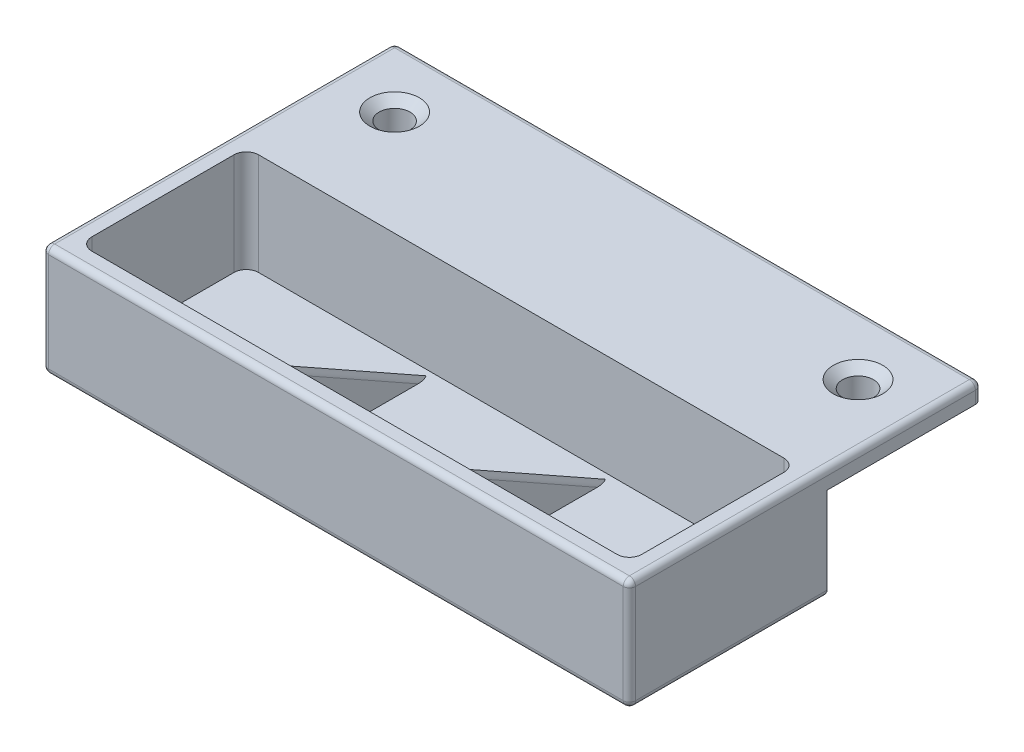
SolidWorks part; units mm, degrees
ref_plane "Front Plane" through (0, 0, 0) normal (0, 0, 1) x (1, 0, 0)
ref_plane "Top Plane" through (0, 0, 0) normal (0, 1, 0) x (1, 0, 0)
ref_plane "Right Plane" through (0, 0, 0) normal (1, 0, 0) x (0, 0, -1)
sketch "Sketch2" plane through (0, 0, 0) normal (0, 1, 0) x (1, 0, 0)
  line L1 (-47.5, 28.5) -> (47.5, 28.5)
  line L2 (-47.5, 28.5) -> (-47.5, -28.5)
  line L3 (-47.5, -28.5) -> (47.5, -28.5)
  line L4 (47.5, 28.5) -> (47.5, -28.5)
  line L5 (-47.5, 28.5) -> (47.5, -28.5) construction
  line L6 (-47.5, -28.5) -> (47.5, 28.5) construction
  point P0 (0, 0)
  dimension "D1" = 95
  dimension "D2" = 57
extrude "Boss-Extrude1" add sketch "Sketch2" along normal blind 18
sketch "Sketch3" plane through (47.5, 0, 0) normal (1, 0, 0) x (0, 0, -1)
  line L1 (28.5, 0) -> (3.5, 0)
  line L2 (28.5, 0) -> (28.5, 15)
  line L3 (28.5, 15) -> (3.5, 15)
  line L4 (3.5, 0) -> (3.5, 15)
  dimension "D1" = 15
  dimension "D2" = 25
extrude "Cut-Extrude1" cut sketch "Sketch3" against normal through all
sketch "Sketch4" plane through (0, 18, 0) normal (0, 1, 0) x (1, 0, 0)
  line L0 (-47.5, 28.5) -> (-47.5, -28.5) construction
  line L1 (-42.5, 1.5) -> (42.5, 1.5)
  line L2 (-44.5, -0.5) -> (-44.5, -23.5)
  line L3 (-42.5, -25.5) -> (42.5, -25.5)
  line L4 (44.5, -0.5) -> (44.5, -23.5)
  line L5 (-47.5, -28.5) -> (47.5, -28.5) construction
  line L6 (47.5, -28.5) -> (47.5, 28.5) construction
  line L7 (47.5, 28.5) -> (-47.5, 28.5) construction
  arc A0 (44.5, -0.5) -> (42.5, 1.5) centre (42.5, -0.5) ccw
  arc A1 (44.5, -23.5) -> (42.5, -25.5) centre (42.5, -23.5) cw
  arc A2 (-42.5, -25.5) -> (-44.5, -23.5) centre (-42.5, -23.5) cw
  arc A3 (-42.5, 1.5) -> (-44.5, -0.5) centre (-42.5, -0.5) ccw
  dimension "D5" = 2
  dimension "D1" = 3
  dimension "D2" = 3
  dimension "D3" = 3
  dimension "D4" = 27
extrude "Cut-Extrude2" cut sketch "Sketch4" against normal blind 16.5
sketch "Sketch5" plane through (0, 18, 0) normal (0, 1, 0) x (1, 0, 0)
  line L0 (-47.5, 28.5) -> (-47.5, -28.5) construction
  line L1 (47.5, 28.5) -> (-47.5, 28.5) construction
  line L2 (47.5, -28.5) -> (47.5, 28.5) construction
  point P0 (-37.5, 18.5)
  point P1 (37.5, 18.5)
  dimension "D1" = 10
  dimension "D2" = 10
  dimension "D3" = 10
  dimension "D4" = 10
sketch "Sketch14" plane through (0, 15, 0) normal (0, -1, 0) x (-1, 0, 0)
  circle A0 centre (37.5, 18.5) radius 6
  circle A1 centre (-37.5, 18.5) radius 6
extrude "Boss-Extrude3" add sketch "Sketch14" along normal blind 2
hole_wizard "CSK for #4 Flat Head Machine Screw (100)3" positions "3DSketch6" profile "Sketch15" countersink size "#4" standard "ANSI Inch" end condition through all
sketch3d "3DSketch6"
  point P0 (37.5, 18, -18.5)
  point P3 (-37.5, 18, -18.5)
sketch "Sketch15" plane through (37.5, 18, -18.5) normal (1, 0, 0) x (0, 0, 1)
  line L0 (0, 0) -> (0, 18)
  line L1 (0, 18) -> (2.5, 18)
  line L2 (2.5, 18) -> (2.5, 1.2586)
  line L3 (2.5, 1.2586) -> (4, 0)
  line L5 (4, 0) -> (0, 0)
  line L6 (-2.5, 1.2586) -> (-4, 0) construction
  line L11 (0, -6.35) -> (0, 107.95) construction
  dimension "Thru Hole Dia." = 5
  dimension "Thru Hole Depth" = 18
  dimension "Near C'Sink Dia." = 8
  dimension "Near C'Sink Angle" = 100
ref_plane "Plane1" through (14.5, 0, 0) normal (-1, 0, 0) x (0, 0, 1)
sketch "Sketch21" plane through (14.5, 0, 0) normal (-1, 0, 0) x (0, 0, 1)
  line L0 (-3.5, 0) -> (28.5, 18)
rib "Rib3" sketch "Sketch21" sketch "Sketch21" thickness 1 extrusion direction parallel to sketch draft on no parameters "D1"=1
ref_plane "Plane4" through (-14.5, 0, 0) normal (1, 0, 0) x (0, 0, -1)
sketch "Sketch23" plane through (-14.5, 0, 0) normal (1, 0, 0) x (0, 0, -1)
  line L0 (-28.5, 18) -> (3.5, 0)
rib "Rib11" sketch "Sketch23" sketch "Sketch23" thickness 1 extrusion direction parallel to sketch draft on no parameters "D1"=1
fillet "Fillet1" radius 1 4 edges at (-15, 8.9062, 12.3333) (-14, 8.9062, 12.3333) (14, 8.9062, 12.3333) (15, 8.9062, 12.3333)
fillet "Fillet2" radius 1 9 edges at (0, 0, 28.5) (-47.5, 9, 28.5) (0, 18, 28.5) (47.5, 9, 28.5) (-47.5, 16.5, -28.5) (-47.5, 18, 0) (0, 18, -28.5) (47.5, 18, 0) (47.5, 16.5, -28.5)
fillet "Fillet3" radius 1 5 edges at (-47.2071, 0.2929, 28.2071) (47.2071, 0.2929, 28.2071) (0, 0, -3.5) (-47.5, 0, 12) (47.5, 0, 12)
